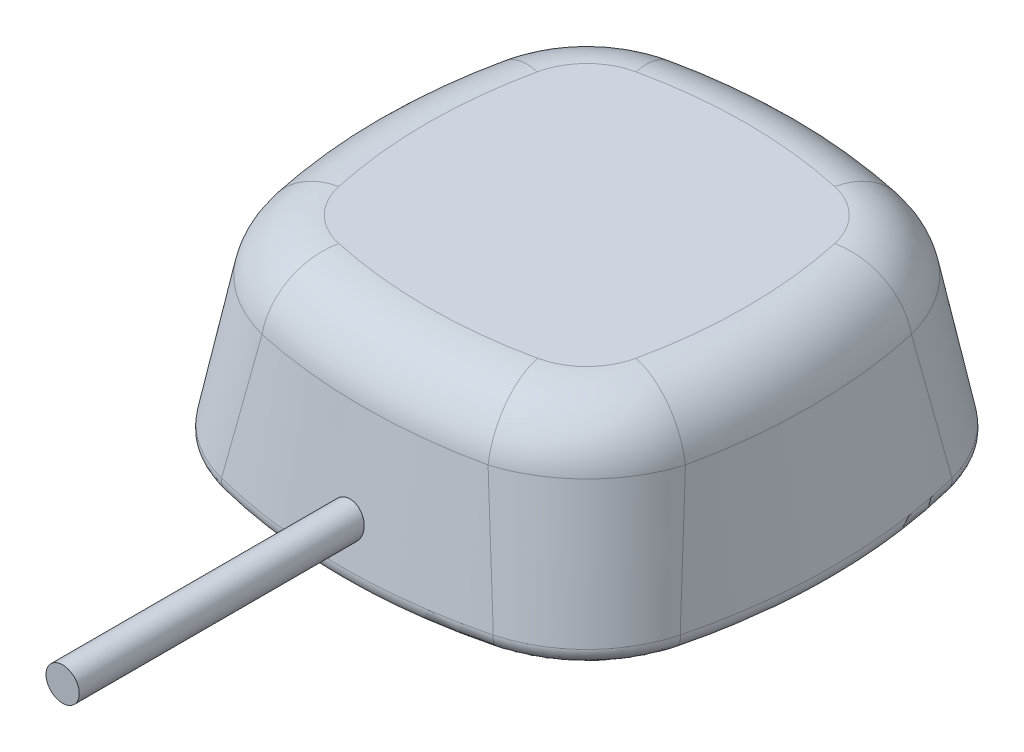
SolidWorks part; units mm, degrees
ref_plane "Front" through (0, 0, 0) normal (0, 0, 1) x (1, 0, 0)
ref_plane "Top" through (0, 0, 0) normal (0, 1, 0) x (1, 0, 0)
ref_plane "Right" through (0, 0, 0) normal (1, 0, 0) x (0, 0, -1)
sketch "Sketch1" plane through (0, 0, 0) normal (0, 1, 0) x (1, 0, 0)
  line L0 (0, 23.5025) -> (0, -23.5025) construction
  line L1 (-23.5025, 0) -> (23.5025, 0) construction
  line L2 (-15.9099, 15.9099) -> (15.9099, -15.9099) construction
  line L3 (15.9099, 15.9099) -> (-15.9099, -15.9099) construction
  line L4 (-19, 0) -> (19, 0) construction
  arc A0 (-15.9099, 15.9099) -> (-15.9099, -15.9099) centre (23.5025, 0) ccw
  arc A1 (15.9099, 15.9099) -> (15.9099, -15.9099) centre (-23.5025, 0) cw
  arc A2 (15.9099, 15.9099) -> (-15.9099, 15.9099) centre (0, -23.5025) ccw
  arc A3 (-15.9099, -15.9099) -> (15.9099, -15.9099) centre (0, 23.5025) ccw
  dimension "D1" = 38
  dimension "D2" = 90
  dimension "D3" = 45
extrude "Boss-Extrude1" add sketch "Sketch1" along normal blind 15
draft "Draft1" type of draft neutral plane draft angle 10 faces to draft 4 face at (0, 7.5, 17.455) face at (-17.455, 7.5, 0) face at (0, 7.5, -17.455) face at (17.455, 7.5, 0) neutral plane through (11.7512, 0, 11.7512) neutral plane normal (0, -1, 0) reverse direction yes parameters "D1"=10
fillet "Fillet1" radius 10 4 edges
fillet "Fillet2" radius 5 8 edges at (-12.2426, 15, 13.4737) (-16.3551, 15, 0) (-13.4737, 15, -12.2426) (0, 15, -16.3551) (12.2426, 15, -13.4737) (16.3551, 15, 0) (13.4737, 15, 12.2426) (0, 15, 16.3551)
fillet "Fillet3" radius 1 8 edges at (-16.0003, 0, 14.0435) (-19, 0, 0) (-14.0435, 0, -16.0003) (0, 0, -19) (16.0003, 0, -14.0435) (19, 0, 0) (14.0435, 0, 16.0003) (0, 0, 19)
sketch "Sketch2" plane through (0, 0, 0) normal (0, 0, 1) x (1, 0, 0)
  line L0 (0, 0) -> (0, 4) construction
  circle A0 centre (0, 4) radius 1.27
  dimension "D1" = 2.54
  dimension "D2" = 4
extrude "Boss-Extrude2" add sketch "Sketch2" along normal blind 40
